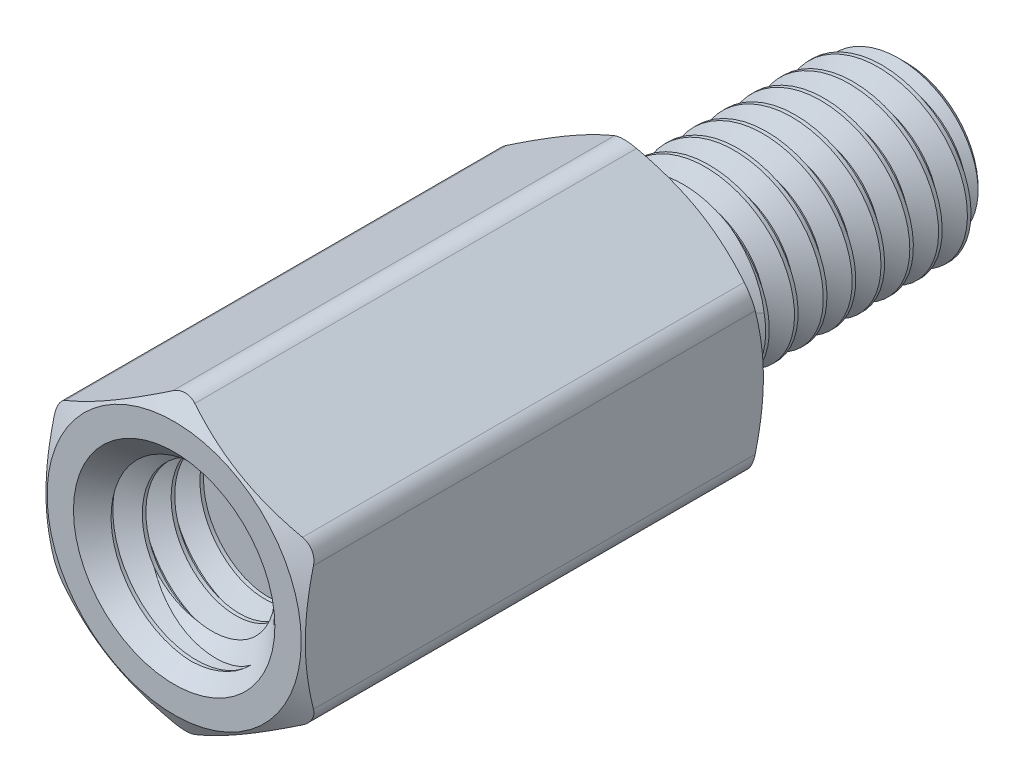
SolidWorks part; units mm, degrees
ref_plane "Front Plane" through (0, 0, 0) normal (0, 0, 1) x (1, 0, 0)
ref_plane "Top Plane" through (0, 0, 0) normal (0, 1, 0) x (1, 0, 0)
ref_plane "Right Plane" through (0, 0, 0) normal (1, 0, 0) x (0, 0, -1)
sketch "Sketch1" plane through (0, 0, 0) normal (0, 0, 1) x (1, 0, 0)
  line L1 (2.25, 1.299) -> (0, 2.5981)
  line L2 (0, 2.5981) -> (-2.25, 1.299)
  line L3 (-2.25, 1.299) -> (-2.25, -1.299)
  line L4 (-2.25, -1.299) -> (0, -2.5981)
  line L5 (0, -2.5981) -> (2.25, -1.299)
  line L6 (2.25, -1.299) -> (2.25, 1.299)
  circle A0 centre (0, 0) radius 2.25 construction
  point P10 (0, -2.25)
  dimension "Hex Size" = 4.5
sketch "Sketch2" plane through (0, 0, 0) normal (1, 0, 0) x (0, 0, -1)
  line L0 (4.7, 0) -> (-8, 0) construction
  line L2 (0, 1.5) -> (0, -1.5) construction
  line L3 (-6.2, 1.5) -> (-6.2, -1.5) construction
  line L4 (-8.4688, 1.5541) -> (-8.2188, 1.1211) construction
  line L5 (-8.2188, 1.1211) -> (-7.9688, 1.5541) construction
  line L6 (-7.9688, 1.5541) -> (-8.4688, 1.5541) construction
  line L7 (-8.4375, 1.5) -> (-8, 1.5) construction
  line L8 (-8.25, 1.1752) -> (-8.1875, 1.1752) construction
  line L9 (-8.2188, 1.1752) -> (-8.2188, 1.1211) construction
  line L10 (-8.2188, 1.5) -> (-8.2188, 1.5541) construction
  line L11 (4.6688, 1.5541) -> (5.1688, 1.5541) construction
  line L12 (5.1688, 1.5541) -> (4.9188, 1.1211) construction
  line L13 (4.9188, 1.1211) -> (4.6688, 1.5541) construction
  line L14 (4.7, 1.5) -> (5.1375, 1.5) construction
  line L15 (4.8875, 1.1752) -> (4.95, 1.1752) construction
  line L16 (4.9188, 1.1752) -> (4.9188, 1.1211) construction
  line L17 (4.9188, 1.5) -> (4.9188, 1.5541) construction
  line L18 (0, 2.5981) -> (-8, 2.5981) construction
  point P6 (0, 0)
  point P9 (-6.2, 0)
  dimension "Length" = 8
sketch "Sketch3" plane through (0, 0, 0) normal (1, 0, 0) x (0, 0, -1)
  line L0 (-6.2, 0) -> (4.7, 0)
  line L1 (-6.2, 1.5) -> (-6.2, -1.5) construction
  line L2 (4.7, 0) -> (4.7, 1.25)
  line L3 (4.7, 1.25) -> (4.45, 1.5)
  line L4 (4.45, 1.5) -> (0.7515, 1.5)
  line L5 (0.7515, 1.5) -> (0.564, 1.1752)
  line L6 (-6.2, 0) -> (-6.2, 1.25)
  line L7 (-6.2, 1.25) -> (-6.45, 1.5)
  line L8 (-6.45, 1.5) -> (-7.75, 1.5)
  line L9 (-7.75, 1.5) -> (-8, 1.75)
  line L10 (4.45, 0) -> (4.45, -1.5) construction
  line L11 (-8, 1.75) -> (-8, 2.25)
  line L12 (-8, 2.25) -> (0, 2.25)
  line L14 (0.564, 1.1752) -> (0.25, 1.1752)
  line L15 (0, 1.4252) -> (0, 2.25)
  arc A0 (0, 1.4252) -> (0.25, 1.1752) centre (0.25, 1.4252) ccw
  point P5 (-8, -2.25)
  point P8 (-6.75, -1.5)
  point P9 (3.45, -1.5)
  point P27 (0, 1.1752)
  dimension "D4" = 0.25
  dimension "D2" = 0.25
  dimension "D1" = 45
  dimension "D6" = 1.25
  dimension "D7" = 60
  dimension "D3" = 1.25
  dimension "D5" = 0.564
revolve "Revolve1" add sketch "Sketch3" angle 360 about L0 region at (0, 1.0485, 1.6468)
sketch "Sketch4" plane through (0, 0, 8) normal (0, 0, 1) x (1, 0, 0)
  line L0 (0, 2.25) -> (0, 1.5) construction
  line L1 (-2.25, 1.299) -> (-2.25, -1.299)
  line L2 (-2.25, -1.299) -> (0, -2.5981)
  line L3 (0, -2.5981) -> (2.25, -1.299)
  line L4 (2.25, -1.299) -> (2.25, 1.299)
  line L5 (2.25, 1.299) -> (0, 2.5981)
  line L6 (0, 2.5981) -> (-2.25, 1.299)
  circle A0 centre (0, 0) radius 2.25 construction
  circle A1 centre (0, 0) radius 1.875
  circle A2 centre (0, 0) radius 2.25 construction
  point P16 (0, 1.875)
extrude "Boss-Extrude1" add sketch "Sketch4" against normal up to surface (8 mm away) up to face at (0, 2.25, 0)
sketch "Sketch5" plane through (0, 0, 8) normal (0, 0, 1) x (1, 0, 0)
  line L0 (-0.8604, 1.2287) -> (0.8604, -1.2287) construction
  line L1 (0, 1.5) -> (0, -1.5) construction
  line L3 (0, -55) -> (0, 55) construction
  circle A0 centre (0, 0) radius 2.205
  point P11 (0.8604, -1.2287)
  dimension "D1" = 4.41
  dimension "D2" = 35
extrude "Cut-Extrude1" cut sketch "Sketch5" against normal through all draft 60 flip side to cut
sketch "Sketch6" plane through (0, 0, 0) normal (0, 0, -1) x (-1, 0, 0)
  circle A0 centre (0, 0) radius 2.205
  circle A1 centre (0, 0) radius 2.205 construction
extrude "Cut-Extrude2" cut sketch "Sketch6" against normal through all draft 60 flip side to cut
fillet "Fillet1" radius 0.3825 6 edges at (0, 2.5981, 4) (-2.25, -1.299, 4) (0, -2.5981, 4) (2.25, -1.299, 4) (2.25, 1.299, 4) (-2.25, 1.299, 4)
sketch "Drawing1" plane through (0, 0, 0) normal (1, 0, 0) x (0, 0, -1)
  line L0 (-8, 1.5) -> (-6.2, 1.5) construction
  line L1 (-6.2, 1.5) -> (-6.2, -1.5) construction
  line L2 (-6.2, -1.5) -> (-8, -1.5) construction
sketch "Sketch7" plane through (0, 0, 0) normal (-1, 0, 0) x (0, 0, 1)
  line L0 (-4.8875, 1.1752) -> (-4.95, 1.1752)
  line L1 (-4.95, 1.1752) -> (-5.1531, 1.5271)
  line L2 (-5.1688, 1.5541) -> (-4.9188, 1.1211) construction
  line L3 (-5.1531, 1.5271) -> (-4.6844, 1.5271)
  line L4 (-4.9188, 1.1211) -> (-4.6688, 1.5541) construction
  line L5 (-4.6844, 1.5271) -> (-4.8875, 1.1752)
  line L6 (-4.9188, 1.5) -> (-4.9188, 1.5541) construction
  point P12 (-4.9188, 1.5271)
sketch "Sketch8" plane through (0, 0, -4.7) normal (0, 0, -1) x (-1, 0, 0)
  circle A0 centre (0, 0) radius 1.5
curve "Helix/Spiral1" pitch 0.5 height 4.559 radius 1.5 centre (0, 0, -4.7) axis (0, 0, 1) start towards (0, 1, 0)
sweep "Cut-Sweep1" cut profiles "Sketch7" path "Helix/Spiral1" align with end faces yes
sketch "Sketch9" plane through (0, 0, 6.2) normal (0, 0, 1) x (1, 0, 0)
  circle A0 centre (0, 0) radius 1.75
extrude "Boss-Extrude2" add sketch "Sketch9" along normal up to surface (1.8 mm away) up to face at (0, 1.75, 8)
sketch "Sketch10" plane through (0, 0, 0) normal (1, 0, 0) x (0, 0, -1)
  line L0 (4.7, 0) -> (-8, 0) construction
  line L1 (-6.2, 1.5) -> (-8, 1.5)
  line L2 (-6.2, 1.5) -> (-6.2, 0)
  line L3 (-6.2, 0) -> (-8, 0)
  line L4 (-8, 1.5) -> (-8, 0)
revolve "Revolve2" add sketch "Sketch10" angle 360 about L0
sketch "Sketch11" plane through (0, 0, 8) normal (0, 0, 1) x (1, 0, 0)
  circle A0 centre (0, 0) radius 1.5
  circle A1 centre (0, 0) radius 1.5 construction
sketch "Sketch12" plane through (0, 0, 0) normal (1, 0, 0) x (0, 0, -1)
  line L0 (-8.25, 1.1752) -> (-8.1875, 1.1752)
  line L1 (-8.1875, 1.1752) -> (-7.9844, 1.5271)
  line L2 (-8.2188, 1.1211) -> (-7.9688, 1.5541) construction
  line L3 (-7.9844, 1.5271) -> (-8.4531, 1.5271)
  line L4 (-8.4688, 1.5541) -> (-8.2188, 1.1211) construction
  line L5 (-8.4531, 1.5271) -> (-8.25, 1.1752)
  line L6 (-8.2188, 1.5) -> (-8.2188, 1.5541) construction
  point P12 (-8.2188, 1.5271)
curve "Helix/Spiral2" pitch 0.5 height 2.3 radius 1.5 centre (0, 0, 8) axis (0, 0, -1) start towards (0, 1, 0)
sweep "Cut-Sweep2" cut profiles "Sketch12" path "Helix/Spiral2" align with end faces yes
combine bodies "Combine1" operation type subtract main body 113 bodies to subtract 114
sketch "Sketch13" plane through (0, 0, 8) normal (0, 0, 1) x (1, 0, 0)
  circle A0 centre (0, 0) radius 1.7475
  dimension "D1" = 3.495
extrude "Cut-Extrude3" cut sketch "Sketch13" against normal through all draft 45
equation "\"Thread Pitch (B)/8@Sketch2\" = \"Thread Pitch (B)@Sketch2\" / 8"
equation "\"Thread Pitch (A)/8@Sketch2\" = \"Thread Pitch (A)@Sketch2\" / 8"
equation "\"D1@Sketch5\"=\"Hex Size@Sketch1\" * .98"
equation "\"D1@Fillet1\"=\"Hex Size@Sketch1\" * .085"
equation "\"D2@Sketch3\"=\"Thread Pitch (A)@Sketch2\" * .5"
equation "\"D4@Sketch3\" = \"D2@Sketch3\""
equation "\"D6@Sketch3\" = \"Thread Pitch (A)@Sketch2\" * 2.5"
equation "\"D3@Helix/Spiral1\" = \"Thread Length (A)@Sketch2\" - \"D5@Sketch3\" * .25"
equation "\"D4@Helix/Spiral1\" = \"Thread Pitch (A)@Sketch2\""
equation "\"D3@Sketch3\" = \"Thread Pitch (B)@Sketch2\" * 2.5"
equation "\"D5@Sketch3\" = \"Thread Length (A)@Sketch2\" * .12"
equation "\"D3@Helix/Spiral2\" = \"Minimum Thread Length (B)@Sketch2\" + \"Thread Pitch (B)@Sketch2\""
equation "\"D4@Helix/Spiral2\" = \"Thread Pitch (B)@Sketch2\""
equation "\"D1@Sketch13\"=(\"Hex Size@Sketch1\"-\"Thread Size (A)@Sketch2\")*.33+\"Thread Size (A)@Sketch2\""
